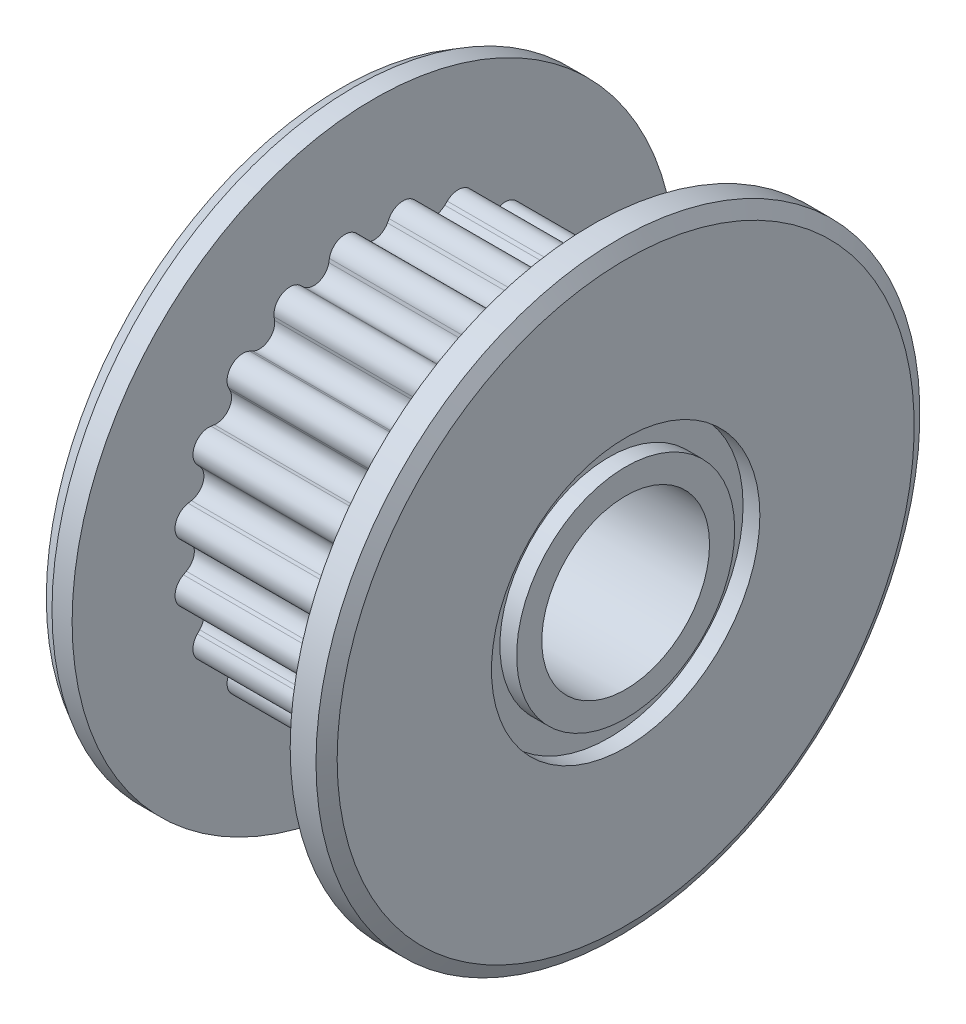
SolidWorks part; units mm, degrees
ref_plane "Front Plane" through (0, 0, 0) normal (0, 0, 1) x (1, 0, 0)
ref_plane "Top Plane" through (0, 0, 0) normal (0, 1, 0) x (1, 0, 0)
ref_plane "Right Plane" through (0, 0, 0) normal (1, 0, 0) x (0, 0, -1)
sketch "Sketch1" plane through (0, 0, 0) normal (0, 0, 1) x (1, 0, 0)
  line L0 (0, 0) -> (8.5, 0) construction
  line L1 (0, 0) -> (0, 9)
  line L2 (0, 9) -> (1, 9)
  line L3 (1, 9) -> (1, 6)
  line L4 (1, 6) -> (7.5, 6)
  line L5 (7.5, 6) -> (7.5, 9)
  line L6 (7.5, 9) -> (8.5, 9)
  line L7 (8.5, 9) -> (8.5, 0)
  line L8 (0, 0) -> (8.5, 0)
  dimension "D1" = 8.5
  dimension "D2" = 18
  dimension "D3" = 12
  dimension "D4" = 6.5
revolve "Revolve1" add sketch "Sketch1" angle 360 about L0
chamfer "Chamfer1" distance 0.4 angle 30 2 edges at (0, 0, 9) (8.5, 0, 9) first distance on face at (0, 0, 9) first distance on face at (8.5, 0, 9)
sketch "Sketch2" plane through (8.5, 0, 0) normal (1, 0, 0) x (0, 0, -1)
  circle A0 centre (0, 0) radius 2.5
  dimension "D1" = 5
extrude "Cut-Extrude1" cut sketch "Sketch2" against normal through all
sketch "Sketch3" plane through (8.5, 0, 0) normal (1, 0, 0) x (0, 0, -1)
  circle A0 centre (0, 0) radius 3.25
  circle A1 centre (0, 0) radius 4
  dimension "D1" = 8
  dimension "D2" = 6.5
extrude "Cut-Extrude2" cut sketch "Sketch3" against normal blind 0.5
sketch "Sketch4" plane through (0, 0, 0) normal (-1, 0, 0) x (0, 0, 1)
  circle A0 centre (0, 0) radius 3.25
  circle A1 centre (0, 0) radius 4
  dimension "D1" = 8
  dimension "D2" = 6.5
extrude "Cut-Extrude3" cut sketch "Sketch4" against normal blind 0.5
sketch "Sketch5" plane through (8.5, 0, 0) normal (1, 0, 0) x (0, 0, -1)
  line L0 (0, 0) -> (0, 3.3722) construction
  line L1 (0, 0) -> (-1.3453, 8.4941) construction
  line L2 (0, 0) -> (1.3453, 8.4941) construction
  line L3 (-0.3995, 5.5946) -> (-0.4473, 5.6832)
  line L4 (0, 0) -> (0, 8.6) construction
  line L5 (0, 5.3564) -> (0, 5.8104) construction
  line L6 (-0.4473, 5.6832) -> (0, 0) construction
  line L7 (0, 5.8104) -> (0, 6) construction
  line L8 (0, 8.6278) -> (0, 3.3722) construction
  line L9 (0.4473, 5.6832) -> (0.3995, 5.5946)
  circle A0 centre (0, 0) radius 6 construction
  arc A1 (-0.3995, 5.5946) -> (0.3995, 5.5946) centre (0, 5.8104) ccw
  arc A2 (-0.4473, 5.6832) -> (-0.9386, 5.9261) centre (-0.8644, 5.4578) ccw
  arc A3 (0.9386, 5.9261) -> (0.4473, 5.6832) centre (0.8644, 5.4578) ccw
  arc A4 (0.9386, 5.9261) -> (-0.9386, 5.9261) centre (0, 0) ccw
  circle A5 centre (0, 0) radius 8.6 construction
  dimension "D1" = 6
  dimension "D5" = 18
  dimension "D6" = 9
  dimension "D3" = 5.8104
  dimension "D4" = 0.4741
  dimension "D2" = 4.5
extrude "Cut-Extrude4" cut sketch "Sketch5" against normal blind 6.5 from offset 1 offset against normal yes
ref_axis "Axis1" through (0, 0, 0) along (1, 0, 0)
pattern_circular "CirPattern1" count 20 every 18 about axis through (0, 0, 0) along (1, 0, 0) of "Cut-Extrude4"
sketch "Sketch7" plane through (1, 0, 0) normal (1, 0, 0) x (0, 0, -1)
  circle A0 centre (0, 0) radius 6 construction
  dimension "D1" = 12
